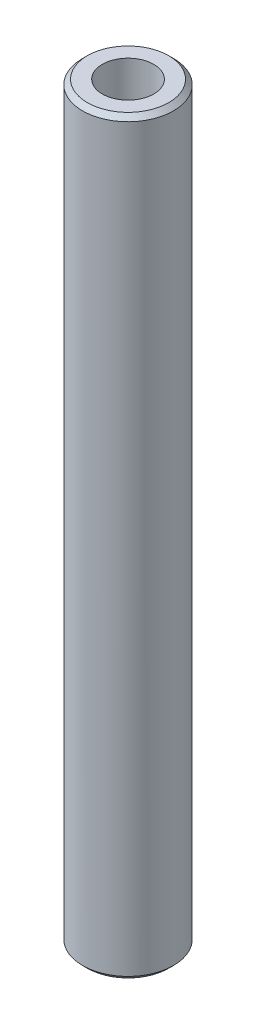
SolidWorks part; units mm, degrees
ref_plane "Front Plane" through (0, 0, 0) normal (0, 0, 1) x (1, 0, 0)
ref_plane "Top Plane" through (0, 0, 0) normal (0, 1, 0) x (1, 0, 0)
ref_plane "Right Plane" through (0, 0, 0) normal (1, 0, 0) x (0, 0, -1)
sketch "Sketch1" plane through (0, 0, 0) normal (0, 1, 0) x (1, 0, 0)
  circle A0 centre (0, 0) radius 30
  dimension "SHAFT_OD" = 60
extrude "Boss-Extrude1" add sketch "Sketch1" along normal blind 494.8194
sketch "Sketch2" plane through (0, 0, 0) normal (0, 1, 0) x (1, 0, 0)
  circle A0 centre (0, 0) radius 16.9814
  dimension "BORE_D" = 33.9628
extrude "Cut-Extrude1" cut sketch "Sketch2" along normal through all
chamfer "Chamfer1" distance 3.1475 angle 45 2 edges at (0, 494.8194, 30) (0, 0, 30)
